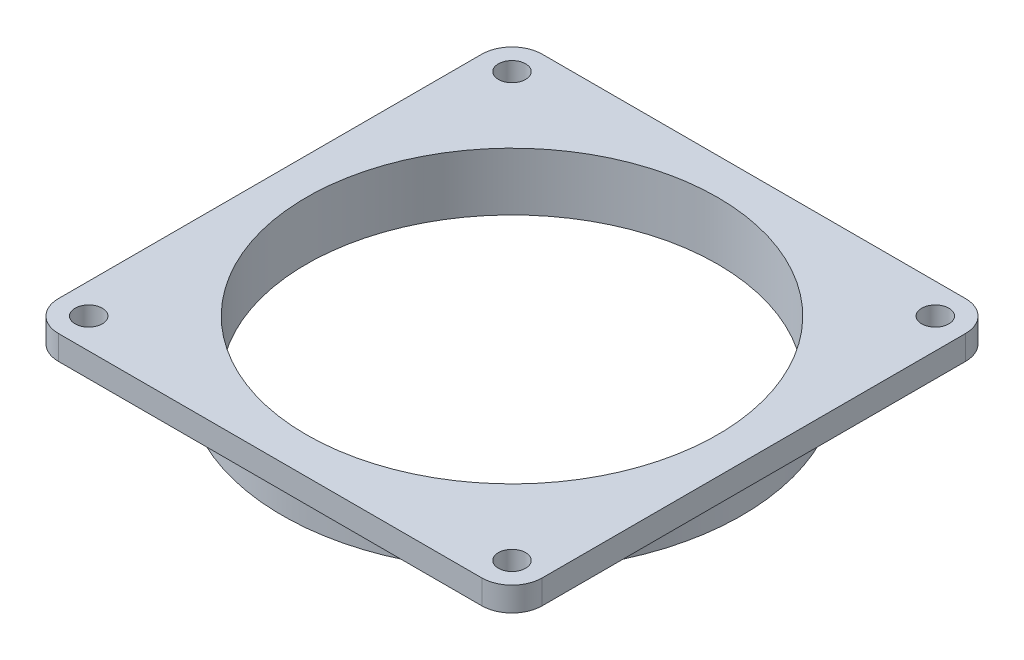
SolidWorks part; units mm, degrees
ref_plane "Front Plane" through (0, 0, 0) normal (0, 0, 1) x (1, 0, 0)
ref_plane "Top Plane" through (0, 0, 0) normal (0, 1, 0) x (1, 0, 0)
ref_plane "Right Plane" through (0, 0, 0) normal (1, 0, 0) x (0, 0, -1)
sketch "Sketch1" plane through (0, 0, 0) normal (0, 1, 0) x (1, 0, 0)
  circle A0 centre (0, 0) radius 34
  circle A2 centre (0, 0) radius 38
extrude "Boss-Extrude1" add sketch "Sketch1" along normal blind 5.5626
sketch "Sketch3" plane through (0, 5.5626, 0) normal (0, 1, 0) x (1, 0, 0)
  line L1 (-35, -35) -> (35, -35)
  line L2 (-35, -35) -> (-35, 35)
  line L3 (-35, 35) -> (35, 35)
  line L4 (35, -35) -> (35, 35)
  line L5 (-35, -35) -> (35, 35) construction
  line L6 (-35, 35) -> (35, -35) construction
  line L7 (40, -40) -> (-40, -40)
  line L8 (40, -40) -> (40, 40)
  line L9 (40, 40) -> (-40, 40)
  line L10 (-40, -40) -> (-40, 40)
  line L11 (40, -40) -> (-40, 40) construction
  line L12 (40, 40) -> (-40, -40) construction
  circle A0 centre (0, 0) radius 34
  circle A1 centre (-35, 35) radius 2.25
  circle A2 centre (35, 35) radius 2.25
  circle A3 centre (35, -35) radius 2.25
  circle A4 centre (-35, -35) radius 2.25
  circle M8 centre (0, 0) radius 38
  circle M9 centre (0, 0) radius 34
  dimension "D1" = 70
  dimension "D2" = 70
  dimension "D3" = 5
  dimension "D4" = 5
extrude "Boss-Extrude5" add sketch "Sketch3" along normal blind 4 contours L2 M8 | L4 L3 L2 L1 M8 M9 | L1 M8 | L4 M8 | L3 M8 | A2 L3 L4 M8 | A3 L4 L1 M8 | A4 L1 L2 M8 | A1 L2 L3 M8 | L10 L7 L8 L9 A4 L2 A1 L3 A2 L4 A3 L1 M8 region at (-29.0494, 5.5626, 29.0494) region at (-26.1701, 5.5626, 26.1701) region at (0, 5.5626, 36.2042) region at (-36.2042, 5.5626, 0) region at (29.0494, 5.5626, 29.0494) region at (-29.0494, 5.5626, -29.0494) region at (36.2042, 5.5626, 0) region at (0, 5.5626, -36.2042) region at (29.0494, 5.5626, -29.0494) region at (0, 5.5626, 38.8686)
fillet "Fillet2" radius 5 4 edges at (-40, 7.5626, -40) (40, 7.5626, -40) (40, 7.5626, 40) (-40, 7.5626, 40)
